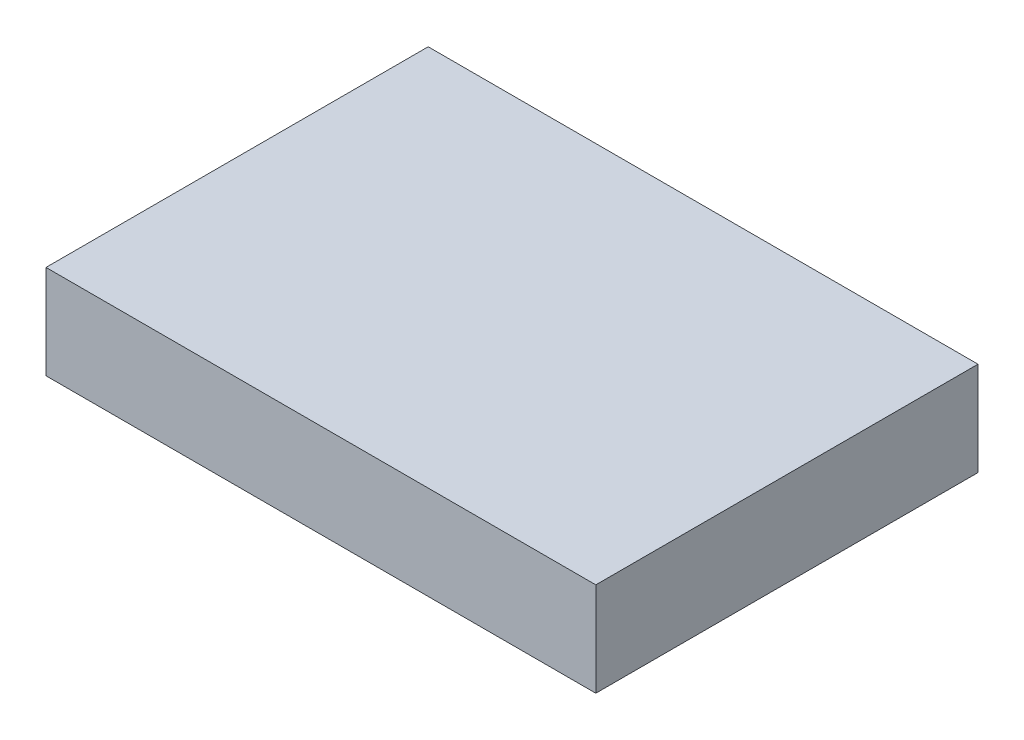
SolidWorks part; units mm, degrees
ref_plane "前视基准面" through (0, 0, 0) normal (0, 0, 1) x (1, 0, 0)
ref_plane "上视基准面" through (0, 0, 0) normal (0, 1, 0) x (1, 0, 0)
ref_plane "右视基准面" through (0, 0, 0) normal (1, 0, 0) x (0, 0, -1)
sketch "草图1" plane through (0, 0, 0) normal (0, 1, 0) x (1, 0, 0)
  line L1 (-41, -28.5) -> (41, -28.5)
  line L2 (-41, -28.5) -> (-41, 28.5)
  line L3 (-41, 28.5) -> (41, 28.5)
  line L4 (41, -28.5) -> (41, 28.5)
  line L5 (-41, -28.5) -> (41, 28.5) construction
  line L6 (-41, 28.5) -> (41, -28.5) construction
  point P0 (0, 0)
  dimension "D1" = 82
  dimension "D2" = 57
extrude "凸台-拉伸1" add sketch "草图1" along normal blind 14
